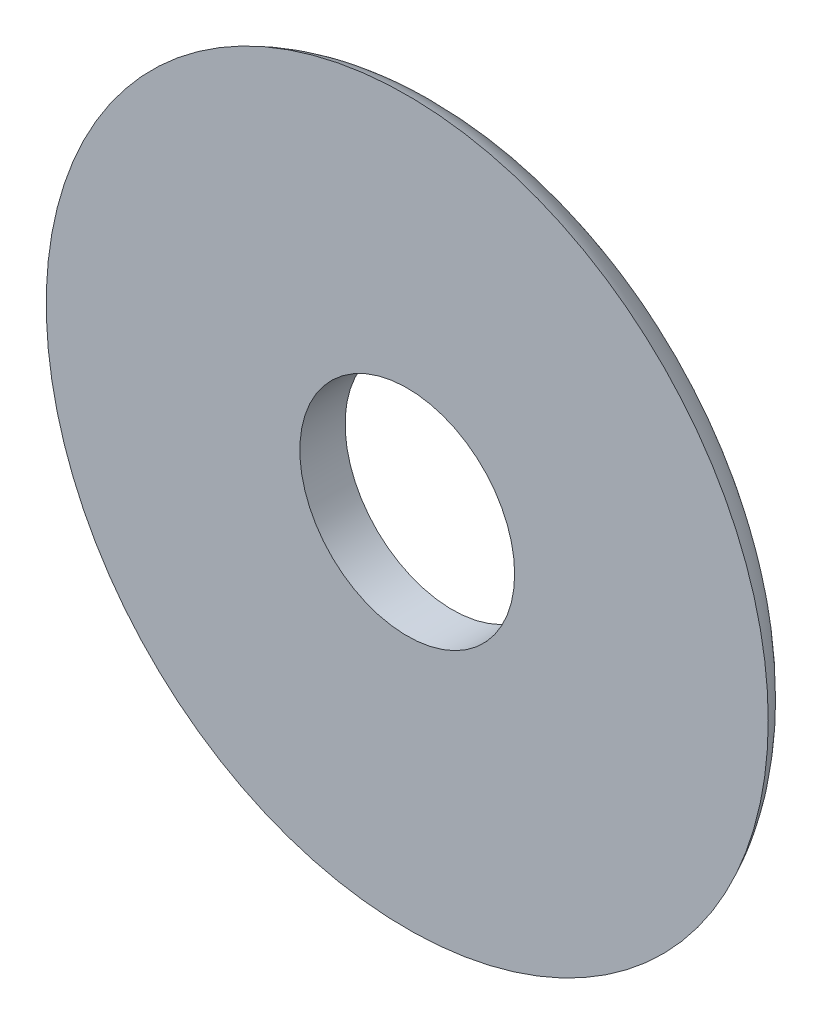
SolidWorks part; units mm, degrees
ref_plane "Front Plane" through (0, 0, 0) normal (0, 0, 1) x (1, 0, 0)
ref_plane "Top Plane" through (0, 0, 0) normal (0, 1, 0) x (1, 0, 0)
ref_plane "Right Plane" through (0, 0, 0) normal (1, 0, 0) x (0, 0, -1)
sketch "Sketch1" plane through (0, 0, 0) normal (0, 0, 1) x (1, 0, 0)
  circle A0 centre (0, 0) radius 47.85
  dimension "D1" = 95.7
extrude "Boss-Extrude1" add sketch "Sketch1" along normal blind 6
sketch "Sketch2" plane through (0, 0, 6) normal (0, 0, 1) x (1, 0, 0)
  circle A0 centre (0, 0) radius 14.235
  dimension "D1" = 28.47
extrude "Cut-Extrude1" cut sketch "Sketch2" against normal blind 6
fillet "Fillet2" radius 10 1 edges at (47.85, 0, 0)
